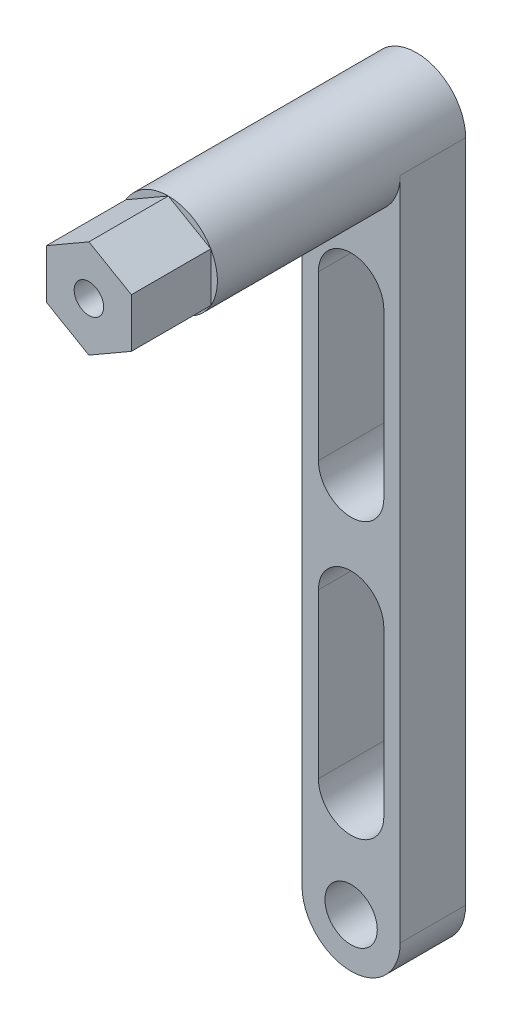
SolidWorks part; units mm, degrees
material "PEI"
ref_plane "Front Plane" through (0, 0, 0) normal (0, 0, 1) x (1, 0, 0)
ref_plane "Top Plane" through (0, 0, 0) normal (0, 1, 0) x (1, 0, 0)
ref_plane "Right Plane" through (0, 0, 0) normal (1, 0, 0) x (0, 0, -1)
sketch "Sketch1" plane through (0, 0, 0) normal (0, 0, 1) x (1, 0, 0)
  line L0 (0, -50.8) -> (0, 50.8) construction
  line L1 (-7.5, -50.8) -> (-7.5, 50.8)
  line L2 (7.5, -50.8) -> (7.5, 50.8)
  line L3 (0, -35.3) -> (0, -10.3) construction
  line L4 (-5, -35.3) -> (-5, -10.3)
  line L5 (5, -35.3) -> (5, -10.3)
  line L6 (0, 31.8) -> (0, 6.8) construction
  line L7 (5, 31.8) -> (5, 6.8)
  line L8 (-5, 31.8) -> (-5, 6.8)
  line L9 (-5, 19.3) -> (5, 19.3) construction
  line L10 (-5, -22.8) -> (5, -22.8) construction
  line L12 (0, 58.3) -> (0, 36.8) construction
  arc A0 (-7.5, -50.8) -> (7.5, -50.8) centre (0, -50.8) ccw
  arc A1 (7.5, 50.8) -> (-7.5, 50.8) centre (0, 50.8) ccw
  circle A2 centre (0, -50.8) radius 4
  arc A4 (-5, -35.3) -> (5, -35.3) centre (0, -35.3) ccw
  arc A5 (5, -10.3) -> (-5, -10.3) centre (0, -10.3) ccw
  arc A6 (5, 31.8) -> (-5, 31.8) centre (0, 31.8) ccw
  arc A7 (-5, 6.8) -> (5, 6.8) centre (0, 6.8) ccw
  circle A8 centre (0, 50.8) radius 7.5
  point P2 (0, 0)
  point P14 (0, -22.8)
  point P19 (0, 19.3)
  point P30 (0, -5.3)
  point P32 (0, -46.8)
  point P33 (0, -40.3)
  point P35 (0, 1.8)
  point P37 (0, 43.3)
  dimension "D3" = 8
  dimension "D1" = 101.6
  dimension "D2" = 15
  dimension "D4" = 10
  dimension "D5" = 6.5
  dimension "20" = 25
  dimension "D6" = 6.5
extrude "Boss-Extrude1" add sketch "Sketch1" along normal blind 10 contours A8 L1 A0 L2 A7 L8 A6 L7 A5 L5 A4 L4 A2 region at (-6.3987, 0, 0)
extrude "Boss-Extrude2" add sketch "Sketch1<4>" along normal blind 37.94 contours A1 A8 region at (0, 50.8, 0)
sketch "Sketch1<4>" plane through (0, 0, 0) normal (0, 0, 1) x (1, 0, 0) same geometry as "Sketch1"
sketch "Sketch2" plane through (0, 0, 37.94) normal (0, 0, 1) x (1, 0, 0)
  point P0 (0, 50.8)
sketch "Sketch3" plane through (0, 0, 37.94) normal (0, 0, 1) x (1, 0, 0)
  line L1 (0, 43.3) -> (6.4952, 47.05)
  line L2 (6.4952, 47.05) -> (6.4952, 54.55)
  line L3 (6.4952, 54.55) -> (0, 58.3)
  line L4 (0, 58.3) -> (-6.4952, 54.55)
  line L5 (-6.4952, 54.55) -> (-6.4952, 47.05)
  line L6 (-6.4952, 47.05) -> (0, 43.3)
  circle A0 centre (0, 50.8) radius 6.4952 construction
extrude "Boss-Extrude3" add sketch "Sketch3" along normal blind 12.14
sketch "Sketch4" plane through (0, 0, 50.08) normal (0, 0, 1) x (1, 0, 0)
  circle A0 centre (0, 50.8) radius 2.25
  dimension "D1" = 4.5
extrude "Cut-Extrude1" cut sketch "Sketch4" against normal blind 10 contours A0
